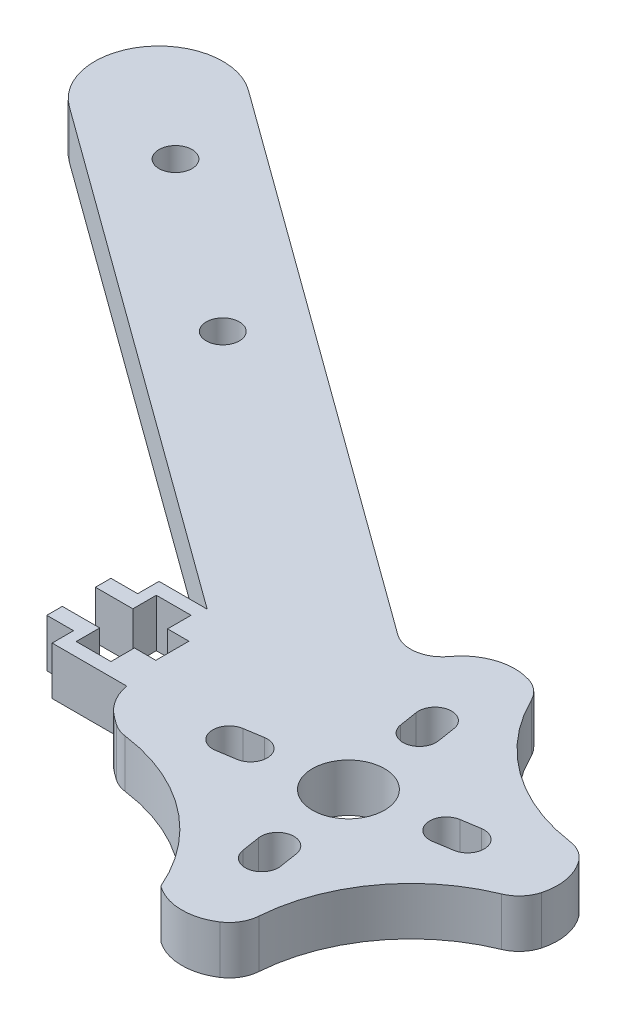
SolidWorks part; units mm, degrees
material "Thornel VCB-20 碳布"
ref_plane "前视基准面" through (0, 0, 0) normal (0, 0, 1) x (1, 0, 0)
ref_plane "上视基准面" through (0, 0, 0) normal (0, 1, 0) x (1, 0, 0)
ref_plane "右视基准面" through (0, 0, 0) normal (1, 0, 0) x (0, 0, -1)
sketch "草图3" plane through (0, 0, 0) normal (0, 1, 0) x (1, 0, 0)
  line L0 (0, 0) -> (35.4735, 0) construction
  line L1 (0, 0) -> (62.3757, -45.3186) construction
  line L2 (41.8666, -23.0015) -> (95.4291, -61.9169)
  line L3 (95.4291, -61.9169) -> (100.1314, -55.4448)
  line L4 (100.1314, -55.4448) -> (122.7839, -71.9028)
  line L5 (122.7839, -71.9028) -> (106.3259, -94.5552)
  line L6 (83.6734, -78.0972) -> (106.3259, -94.5552)
  line L9 (77.9994, -109.7251) -> (128.6275, -40.0415) construction
  line L11 (103.2286, -75) -> (90.242, -77.0569) construction
  line L13 (111.1302, -73.7485) -> (112.8586, -73.4748) construction
  line L14 (110.8877, -72.2176) -> (112.6161, -71.9438)
  line L15 (111.3726, -75.2794) -> (113.1011, -75.0057)
  line L16 (101.9772, -67.0985) -> (101.7034, -65.37) construction
  line L17 (103.5081, -66.856) -> (103.2343, -65.1276)
  line L18 (100.4463, -67.341) -> (100.1725, -65.6125)
  line L19 (95.3271, -76.2515) -> (93.5987, -76.5252) construction
  line L20 (95.5696, -77.7824) -> (93.8412, -78.0562)
  line L21 (95.0847, -74.7206) -> (93.3562, -74.9943)
  line L22 (104.4801, -82.9015) -> (104.7539, -84.63) construction
  line L23 (102.9492, -83.144) -> (103.223, -84.8724)
  line L24 (106.011, -82.659) -> (106.2848, -84.3875)
  line L25 (34.8132, -32.7097) -> (82.0098, -67)
  line L26 (82.0098, -67) -> (77.5, -67)
  line L27 (77.5, -67) -> (77.5, -69)
  line L28 (77.5, -69) -> (75, -69)
  line L29 (75, -69) -> (75, -70.45)
  line L30 (75, -70.45) -> (78.5, -70.45)
  line L31 (78.5, -70.45) -> (78.5, -68.25)
  line L32 (78.5, -68.25) -> (81.75, -68.25)
  line L33 (81.75, -68.25) -> (81.75, -70.45)
  line L34 (81.75, -70.45) -> (83.75, -70.45)
  line L35 (83.75, -70.45) -> (83.75, -73.55)
  line L36 (68.8077, -72) -> (90.242, -72) construction
  line L37 (81.75, -73.55) -> (83.75, -73.55)
  line L38 (81.75, -75.75) -> (81.75, -73.55)
  line L39 (78.5, -75.75) -> (81.75, -75.75)
  line L40 (78.5, -73.55) -> (78.5, -75.75)
  line L41 (75, -73.55) -> (78.5, -73.55)
  line L42 (75, -75) -> (75, -73.55)
  line L43 (77.5, -75) -> (75, -75)
  line L44 (77.5, -77) -> (77.5, -75)
  line L45 (82.0098, -77) -> (77.5, -77)
  line L47 (83.6734, -78.0972) -> (84.4706, -77)
  line L48 (84.4706, -77) -> (82.0098, -77)
  circle A5 centre (103.2286, -75) radius 3.375
  arc A6 (110.8877, -72.2176) -> (111.3726, -75.2794) centre (111.1302, -73.7485) ccw
  arc A7 (113.1011, -75.0057) -> (112.6161, -71.9438) centre (112.8586, -73.4748) ccw
  arc A8 (103.5081, -66.856) -> (100.4463, -67.341) centre (101.9772, -67.0985) cw
  arc A9 (100.1725, -65.6125) -> (103.2343, -65.1276) centre (101.7034, -65.37) cw
  arc A10 (95.5696, -77.7824) -> (95.0847, -74.7206) centre (95.3271, -76.2515) ccw
  arc A11 (93.3562, -74.9943) -> (93.8412, -78.0562) centre (93.5987, -76.5252) ccw
  arc A12 (102.9492, -83.144) -> (106.011, -82.659) centre (104.4801, -82.9015) cw
  arc A13 (106.2848, -84.3875) -> (103.223, -84.8724) centre (104.7539, -84.63) cw
  arc A16 (41.8666, -23.0015) -> (34.8132, -32.7097) centre (38.3399, -27.8556) ccw
  circle A17 centre (103.2286, -75) radius 66.25 construction
  circle A18 centre (44.0442, -32) radius 1.55
  circle A19 centre (60.2246, -43.7557) radius 1.55
  point P11 (114.5549, -83.229)
  point P20 (111.9944, -73.6116)
  point P27 (101.8403, -66.2343)
  point P35 (94.4629, -76.3884)
  point P42 (104.617, -83.7657)
  point P54 (94.9997, -86.3262)
  point P67 (83.75, -72)
  dimension "D2" = 45
  dimension "D3" = 6.75
  dimension "D4" = 1.55
  dimension "D7" = 14
  dimension "D11" = 132.5
  dimension "D12" = 3.1
  dimension "D1" = 36
  dimension "D5" = 1.75
  dimension "D6" = 8
  dimension "D8" = 14
  dimension "D9" = 6
  dimension "D10" = 75
  dimension "D13" = 32
  dimension "D14" = 20
  dimension "D15" = 7.5
  dimension "D16" = 10
  dimension "D17" = 3.1
  dimension "D18" = 3.5
  dimension "D19" = 3.25
  dimension "D20" = 2
  dimension "D21" = 2.5
  dimension "D22" = 72
  dimension "D23" = 75
  dimension "D24" = 1.45
extrude "凸台-拉伸1" add sketch "草图3" along normal blind 4.5
fillet "圆角-美观1" radius 5 4 edges at (100.1314, 2.25, 55.4448) (122.7839, 2.25, 71.9028) (106.3259, 2.25, 94.5552) (83.6734, 2.25, 78.0972)
sketch "草图4" plane through (0, 4.5, 0) normal (0, 1, 0) x (1, 0, 0)
  line L0 (104.1765, -58.3837) -> (118.7388, -68.9638)
  line L1 (119.8449, -75.9478) -> (109.2648, -90.5101)
  line L3 (103.2286, -75) -> (124.6569, -90.5685) construction
  line L4 (103.2286, -75) -> (89.033, -94.5387) construction
  line L5 (87.7185, -81.0362) -> (102.2808, -91.6163)
  arc A2 (102.2808, -91.6163) -> (87.7185, -81.0362) centre (86.1651, -98.4859) ccw
  arc A8 (118.7388, -68.9638) -> (104.1765, -58.3837) centre (120.2922, -51.5141) cw
  arc A9 (119.8449, -75.9478) -> (109.2648, -90.5101) centre (124.6569, -90.5685) ccw
extrude "圆弧-美观2" cut sketch "草图4" against normal up to next
fillet "圆角-美观3" radius 3 6 edges at (104.1765, 2.25, 58.3837) (118.7388, 2.25, 68.9638) (119.8449, 2.25, 75.9478) (109.2648, 2.25, 90.5101) (95.4291, 2.25, 61.9169) (87.7185, 2.25, 81.0362)
